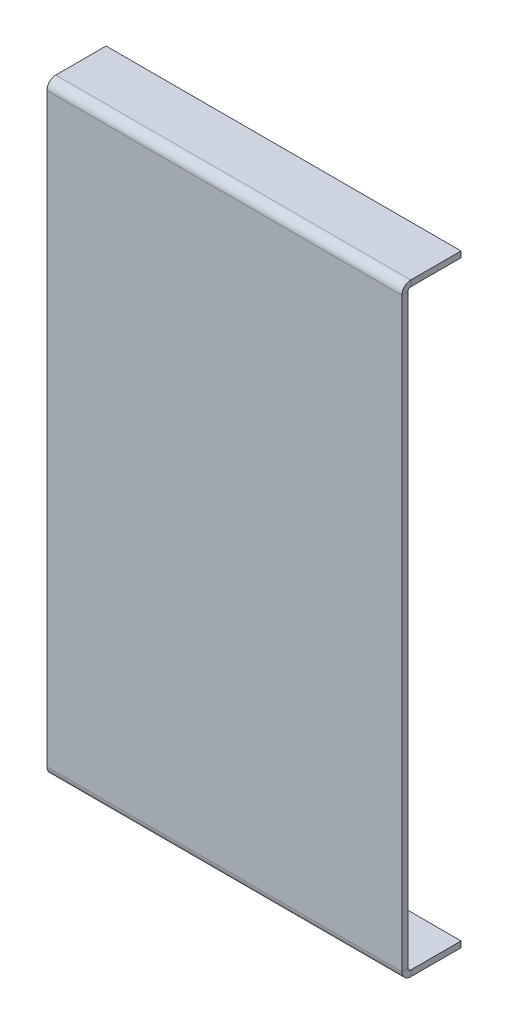
SolidWorks part; units mm, degrees
note: The reader was unsure of these and kept them because the rebuilt part matched: flange length of "边线-法兰1".
ref_plane "前视基准面" through (0, 0, 0) normal (0, 0, 1) x (1, 0, 0)
ref_plane "上视基准面" through (0, 0, 0) normal (0, 1, 0) x (1, 0, 0)
ref_plane "右视基准面" through (0, 0, 0) normal (1, 0, 0) x (0, 0, -1)
sketch "草图1" plane through (0, 0, 0) normal (0, 0, 1) x (1, 0, 0)
  line L1 (-60, 102) -> (60, 102)
  line L2 (-60, 102) -> (-60, -102)
  line L3 (-60, -102) -> (60, -102)
  line L4 (60, 102) -> (60, -102)
  line L5 (-60, 102) -> (60, -102) construction
  line L6 (-60, -102) -> (60, 102) construction
  point P0 (0, 0)
  dimension "D1" = 204
  dimension "D2" = 120
base flange "基体-法兰1" sketch "草图1" thickness 2 reverse thickness direction no parameters "D1"=1
edge flange "边线-法兰1" sketch "草图10" flange profiles "草图10", "草图11" flange angle 90 flange length 20 flange position material inside bend radius 1 thickness 2 relief rectangular parameters "D6"=10, "D8"=1
sketch "草图10" plane through (0, 102, -2) normal (0, -1, 0) x (-1, 0, 0)
  line L1 (60, 0) -> (-60, 0) construction
  line L2 (-60, 0) -> (-60, 18)
  line L3 (-60, 18) -> (60, 18)
  line L4 (60, 18) -> (60, 0)
  line L5 (60, 0) -> (-60, 0)
sketch "草图11" plane through (0, -102, -2) normal (0, 1, 0) x (1, 0, 0)
  line L0 (60, 0) -> (-60, 0) construction
  line L1 (60, 0) -> (-60, 0)
  line L2 (60, 0) -> (60, 18)
  line L3 (60, 18) -> (-60, 18)
  line L4 (-60, 18) -> (-60, 0)
bend "边线折弯1" bend radius 1 bend angle 90 parameters "D5"=1
bend "边线折弯2" bend radius 1 bend angle 90 parameters "D5"=2
sketch "折弯-线1" [suppressed] plane through (0, 0, 0) normal (0, 1, 0) x (1, 0, 0)
sketch "边界框1" [suppressed] plane through (0, 0, 0) normal (0, 1, 0) x (1, 0, 0)
sheet metal parameters "钣金6" thickness 2 parameters "D1"=1
flat pattern "平板型式6" [suppressed]
sketch "折弯-线2" plane through (0, 0, 0) normal (0, 1, 0) x (1, 0, 0)
sketch "边界框2" [suppressed] plane through (0, 0, 0) normal (0, 1, 0) x (1, 0, 0)
sheet metal parameters "钣金7" thickness 2 parameters "D1"=1
flat pattern "平板型式6"
sketch "折弯-线2" plane through (0, 0, 0) normal (0, 0, 1) x (1, 0, 0)
  line L0 (-60, -100.4) -> (60, -100.4) construction
  line L1 (60, 100.4) -> (-60, 100.4) construction
  line L2 (-60, -100.4) -> (60, -100.4) construction
  line L3 (60, 100.4) -> (-60, 100.4) construction
sketch3d "边界框2" [suppressed]
  line L0 (60, 118.8, 0) -> (60, -118.8, 0) construction
  line L1 (-60, 118.8, 0) -> (-60, -118.8, 0) construction
  line L2 (60, 118.8, 0) -> (-60, 118.8, 0) construction
  line L3 (60, -118.8, 0) -> (-60, -118.8, 0) construction
bend of the flat pattern "展开-<边线折弯1>1"
bend of the flat pattern "展开-<边线折弯2>1"
